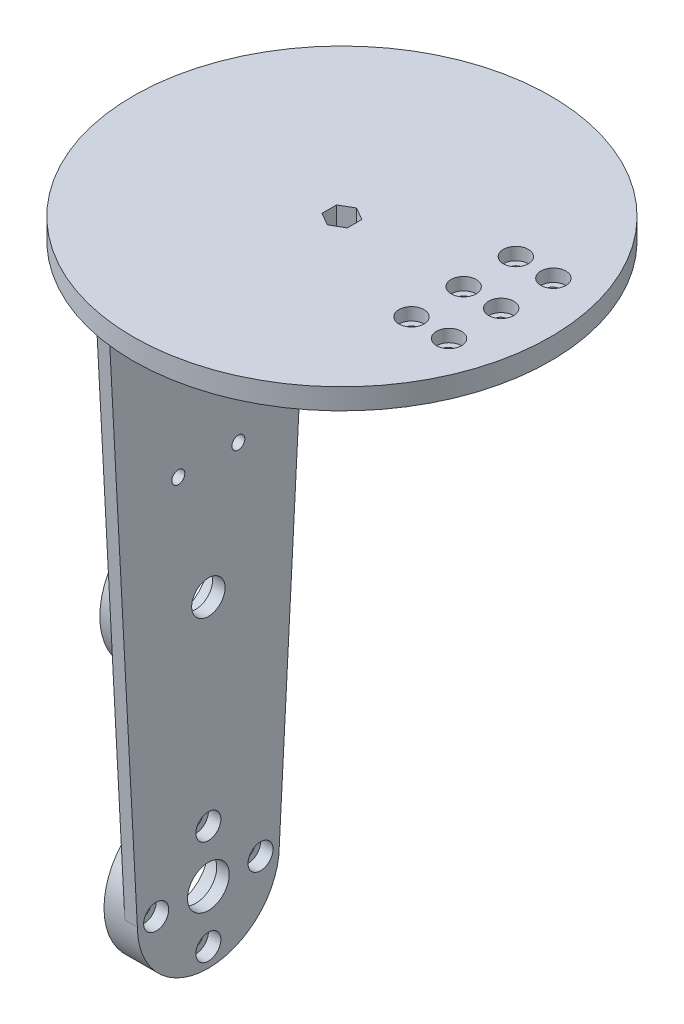
SolidWorks part; units mm, degrees
ref_plane "Front Plane" through (0, 0, 0) normal (0, 0, 1) x (1, 0, 0)
ref_plane "Top Plane" through (0, 0, 0) normal (0, 1, 0) x (1, 0, 0)
ref_plane "Right Plane" through (0, 0, 0) normal (1, 0, 0) x (0, 0, -1)
sketch "Sketch2" plane through (0, 0, 0) normal (0, 1, 0) x (1, 0, 0)
  circle A0 centre (0, 0) radius 9
extrude "Boss-Extrude1" add sketch "Sketch2" along normal blind 20
sketch "Sketch3" plane through (0, 20, 0) normal (0, 1, 0) x (1, 0, 0)
  line L3 (0, 3.5) -> (-3.0311, 1.75)
  line L4 (-3.0311, 1.75) -> (-3.0311, -1.75)
  line L5 (-3.0311, -1.75) -> (0, -3.5)
  line L6 (0, -3.5) -> (3.0311, -1.75)
  line L7 (3.0311, -1.75) -> (3.0311, 1.75)
  line L8 (3.0311, 1.75) -> (0, 3.5)
  point P6 (0, 0)
  point P9 (0, 0)
  point P11 (0, 0)
extrude "Cut-Extrude1" cut sketch "Sketch3" against normal blind 20
sketch "Sketch4" plane through (0, 20, 0) normal (0, 1, 0) x (1, 0, 0)
  circle A0 centre (0, 0) radius 50
  circle A1 centre (0, 0) radius 3.9955
extrude "Boss-Extrude3" add sketch "Sketch4" against normal blind 5
ref_plane "Plane3" through (0, 0, 0) normal (0.5, 0, 0.866) x (0.866, 0, -0.5)
sketch "Sketch11" plane through (0, 0, 0) normal (0.5, 0, 0.866) x (0.866, 0, -0.5)
  line L2 (0, 0) -> (0, 5) construction
  circle A0 centre (0, 5) radius 1.55
extrude "Cut-Extrude2" cut sketch "Sketch11" against normal blind 9 and the other way blind 9
ref_plane "Plane4" through (0, 0, 0) normal (1, 0, 0) x (0, 0, -1)
sketch "Sketch15" plane through (0, 0, 0) normal (1, 0, 0) x (0, 0, -1)
  circle A0 centre (0, 9) radius 1.55
extrude "Cut-Extrude9" cut sketch "Sketch15" against normal blind 9 and the other way blind 9
sketch "Sketch16" plane through (0, 15, 0) normal (0, -1, 0) x (1, 0, 0)
  line L0 (0, 0) -> (32, 0) construction
  line L6 (0, 0) -> (-32, 0) construction
  line L7 (-32, -25) -> (-32, 25) construction
  line L8 (32, 25) -> (32, -25) construction
  line L9 (32, 25) -> (35, 25) construction
  line L10 (32, -25) -> (35, -25) construction
  line L11 (35, 25) -> (35, -25) construction
  line L12 (32, 25) -> (35, -25) construction
  line L13 (32, -25) -> (35, 25) construction
  line L14 (32, 25) -> (26.3083, 25) construction
  line L15 (35, 25) -> (41, 25) construction
  line L16 (29.1541, 25) -> (29.1541, 12.5) construction
  line L17 (29.1541, 12.5) -> (29.1541, 0) construction
  line L18 (29.1541, 0) -> (29.1541, -12.5) construction
  line L19 (38, 25) -> (38, 12.5) construction
  line L20 (38, 12.5) -> (38, 0) construction
  line L21 (38, 0) -> (38, -12.5) construction
  circle A0 centre (29.1541, 12.5) radius 1.55
  circle A1 centre (29.1541, 0) radius 1.55
  circle A2 centre (29.1541, -12.5) radius 1.55
  circle A3 centre (38, -12.5) radius 1.55
  circle A4 centre (38, 0) radius 1.55
  circle A5 centre (38, 12.5) radius 1.55
  point P8 (32, 0)
  point P10 (-32, 0)
  point P14 (33.5, 0)
ref_plane "Plane7" through (-32, 0, 0) normal (-1, 0, 0) x (0, 0, 1)
sketch "Sketch28" plane through (-32, 0, 0) normal (-1, 0, 0) x (0, 0, 1)
  line L0 (25, 15) -> (-25, 15)
  line L1 (0, -135) -> (0, -75) construction
  line L2 (-50, 15) -> (50, 15) construction
  line L3 (0, 15) -> (0, -135) construction
  line L6 (25, 15) -> (17, -135)
  line L7 (-17, -135) -> (-25, 15)
  circle A0 centre (0, -135) radius 5
  circle A3 centre (0, -75) radius 4
  arc A6 (17, -135) -> (-17, -135) centre (0, -135) cw
  circle A8 centre (7.1867, -46.5) radius 1.55
  circle A9 centre (-7.1867, -46.5) radius 1.55
  point P4 (0, 15)
extrude "Boss-Extrude10" add sketch "Sketch28" along normal blind 3
sketch "Sketch25" plane through (-35, 0, 0) normal (-1, 0, 0) x (0, 0, 1)
  circle A6 centre (0, -135) radius 8
  circle A7 centre (0, -135) radius 17
extrude "Boss-Extrude8" add sketch "Sketch25" along normal blind 5
sketch "Sketch26" plane through (-40, 0, 0) normal (-1, 0, 0) x (0, 0, 1)
  circle A12 centre (0, -135) radius 12.5 construction
  circle A16 centre (-12.5, -135) radius 1.55
  circle A17 centre (0, -122.5) radius 1.55
  circle A18 centre (12.5, -135) radius 1.55
  circle A19 centre (0, -147.5) radius 1.55
  point P14 (0, -135)
extrude "Cut-Extrude14" cut sketch "Sketch26" against normal blind 8
sketch "Sketch27" plane through (-32, 0, 0) normal (1, 0, 0) x (0, 0, -1)
  circle A4 centre (0, -135) radius 12.5 construction
  circle A5 centre (-12.5, -135) radius 3
  circle A6 centre (0, -122.5) radius 3
  circle A7 centre (12.5, -135) radius 3
  circle A8 centre (0, -147.5) radius 3
  point P15 (0, -135)
extrude "Cut-Extrude15" cut sketch "Sketch27" against normal blind 3
extrude "Cut-Extrude17" cut sketch "Sketch16" against normal blind 5
sketch "Sketch29" plane through (0, 20, 0) normal (0, 1, 0) x (1, 0, 0)
  circle A0 centre (29.1541, 12.5) radius 3
  circle A1 centre (38.1541, 12.5) radius 3
  circle A2 centre (38.1541, 0) radius 3
  circle A3 centre (38.1541, -12.5) radius 3
  circle A4 centre (29.1541, 0) radius 3
  circle A5 centre (29.1541, -12.5) radius 3
  dimension "D1" = 2
  dimension "D2" = 3
extrude "Cut-Extrude18" cut sketch "Sketch29" against normal blind 3
sketch "Sketch30" plane through (-35, 0, 0) normal (-1, 0, 0) x (0, 0, 1)
  circle A0 centre (0, -75) radius 9.5
  circle A1 centre (0, -75) radius 17
extrude "Boss-Extrude11" add sketch "Sketch30" along normal blind 6
sketch "Sketch31" plane through (0, 0, 0) normal (0.5, 0, 0.866) x (0.866, 0, -0.5)
  circle A1 centre (0, 5) radius 3
extrude "Cut-Extrude23" cut sketch "Sketch31" against normal blind 2.5 from offset 9
extrude "Cut-Extrude24" cut sketch "Sketch31<3>" along normal blind 2.5 from offset 9 offset against normal yes
sketch "Sketch31<3>" plane through (0, 0, 0) normal (0.5, 0, 0.866) x (0.866, 0, -0.5) same geometry as "Sketch31"
sketch "Sketch33" plane through (0, 0, 0) normal (1, 0, 0) x (0, 0, -1)
  circle A0 centre (0, 9) radius 3
extrude "Cut-Extrude25" cut sketch "Sketch33" against normal blind 2.5 from offset 9
extrude "Cut-Extrude26" cut sketch "Sketch33<2>" along normal blind 2.5 from offset 9 offset against normal yes
sketch "Sketch33<2>" plane through (0, 0, 0) normal (1, 0, 0) x (0, 0, -1) same geometry as "Sketch33"
